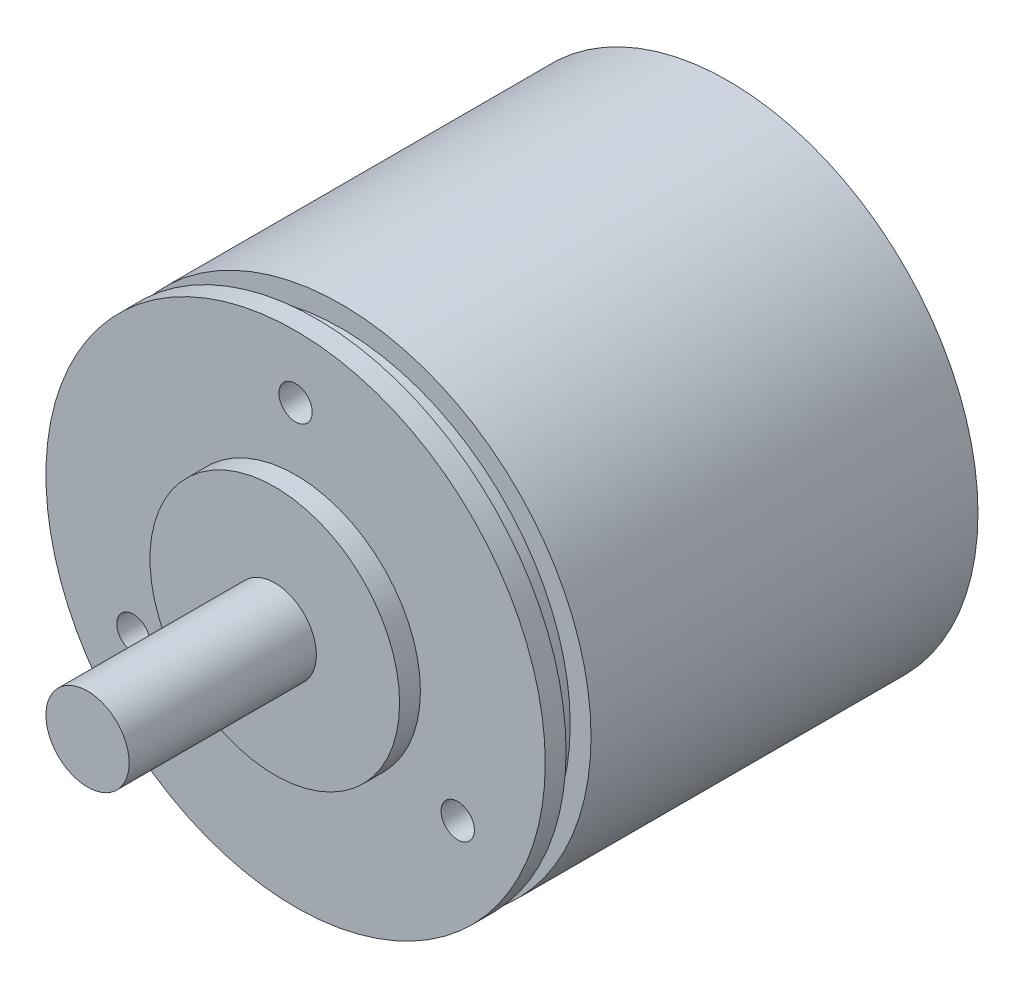
SolidWorks part; units mm, degrees
material "Laiton au plomb 2%, UNS C34200"
ref_plane "Plan de face" through (0, 0, 0) normal (0, 0, 1) x (1, 0, 0)
ref_plane "Plan de dessus" through (0, 0, 0) normal (0, 1, 0) x (1, 0, 0)
ref_plane "Plan de droite" through (0, 0, 0) normal (1, 0, 0) x (0, 0, -1)
sketch "Esquisse1" plane through (0, 0, 0) normal (1, 0, 0) x (0, 0, -1)
  line L0 (-27.8339, 0) -> (36.2865, 0) construction
  line L1 (-9, 0) -> (-9, 2)
  line L2 (-9, 2) -> (0, 2)
  line L3 (0, 2) -> (0, 6)
  line L4 (0, 6) -> (1, 6)
  line L5 (1, 6) -> (1, 12)
  line L6 (1, 12) -> (2, 12)
  line L7 (21.8, 12) -> (21.8, 0)
  line L8 (-9, 0) -> (21.8, 0)
  line L9 (2, 12) -> (2, 11)
  line L10 (2, 11) -> (3.2, 11)
  line L11 (3.2, 11) -> (3.2, 12)
  line L12 (3.2, 12) -> (21.8, 12)
  dimension "D1" = 12
  dimension "D2" = 1
  dimension "D3" = 24
  dimension "D4" = 20.8
  dimension "D5" = 9
  dimension "D6" = 4
  dimension "D7" = 1
  dimension "D8" = 1.2
  dimension "D9" = 1
revolve "Révolution1" add sketch "Esquisse1" angle 360 about L0
hole_wizard "Trou taraudé M2x0.41" positions "Esquisse3" profile "Esquisse2" tap size "M2x0.4" standard "Ansi Métrique"
sketch "Esquisse3" plane through (0, 0, 0) normal (0, 0, 1) x (1, 0, 0)
  circle A0 centre (0, 0) radius 9 construction
  point P0 (-7.7942, -4.5)
  point P1 (7.7942, -4.5)
  point P14 (0, 9)
  dimension "D2" = 120
  dimension "D1" = 18
sketch "Esquisse2" plane through (-7.7942, -4.5, 0) normal (1, 0, 0) x (0, -1, 0)
  line L0 (0, 0) -> (0, 3.6807)
  line L1 (0, 3.6807) -> (0.8, 3.2)
  line L2 (0.8, 3.2) -> (0.8, 0)
  line L5 (0.8, 0) -> (0, 0)
  line L10 (0, 3.6807) -> (-0.8, 3.2) construction
  line L11 (0, -6.35) -> (0, 107.95) construction
  dimension "Diamètre du trou pour taraudage" = 1.6
  dimension "Profondeur du trou pour taraudage" = 3.2
  dimension "Angle de pointe" = 118
cosmetic thread "Filetage de perçage1" parameters "D1"=2, "D2"=2
cosmetic thread "Filetage de perçage2" parameters "D1"=2, "D2"=2
cosmetic thread "Filetage de perçage3" parameters "D1"=2, "D2"=2
ref_axis "Axe1" through (0, 0, -23.34) along (0, 0, 1)
